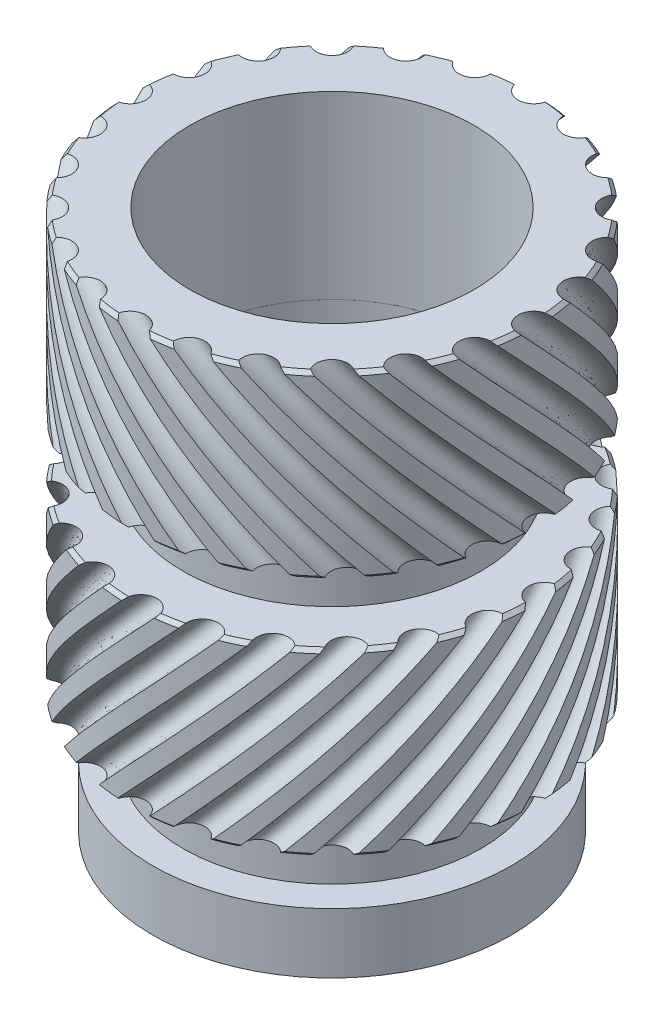
SolidWorks part; units mm, degrees
material "Brass"
ref_plane "Front" through (0, 0, 0) normal (0, 0, 1) x (1, 0, 0)
ref_plane "Top" through (0, 0, 0) normal (0, 1, 0) x (1, 0, 0)
ref_plane "Right" through (0, 0, 0) normal (1, 0, 0) x (0, 0, -1)
sketch "Layout " plane through (0, 0, 0) normal (0, 0, 1) x (1, 0, 0)
  line L0 (0, 0) -> (0, 9.5) construction
  line L1 (2.6222, 1.0556) -> (3.15, 1.0556) construction
  line L2 (3.15, 0) -> (0, 0) construction
  line L3 (3.55, 9.5) -> (3.55, 6.3333) construction
  line L4 (3.55, 6.3333) -> (2.6222, 6.3333) construction
  line L5 (2.6222, 6.3333) -> (2.6222, 5.2778) construction
  line L6 (2.6222, 5.2778) -> (3.55, 5.2778) construction
  line L7 (3.55, 5.2778) -> (3.55, 2.1111) construction
  line L8 (3.55, 2.1111) -> (2.6222, 2.1111) construction
  line L9 (2.6222, 2.1111) -> (2.6222, 1.0556) construction
  line L10 (2.6222, 5.8056) -> (0, 5.8056) construction
  line L11 (3.15, 1.0556) -> (3.15, 0) construction
  line L12 (0, 4.75) -> (2.5, 4.75) construction
  line L14 (3.55, 9.5) -> (3.55, 4.7136) construction
  line L15 (3.55, 9.5) -> (0, 9.5) construction
  line L16 (2.5, 9.5) -> (2.5, 0) construction
  point P19 (0, 8.7)
  dimension "D4" = 0.5278
  dimension "D5" = 3.1667
  dimension "D1" = 0.5278
ref_plane "Plane1" through (0, 5.8056, 0) normal (0, 1, 0) x (1, 0, 0)
sketch "Sketch3" plane through (0, 0, 0) normal (0, 0, 1) x (1, 0, 0)
  line L0 (0, 0) -> (0, 9.5) construction
  line L1 (3.55, 9.5) -> (0, 9.5) construction
  line L2 (3.55, 9.5) -> (3.55, 6.3333) construction
  line L4 (2.6222, 6.3333) -> (2.6222, 5.2778) construction
  line L5 (2.6222, 5.2778) -> (3.55, 5.2778) construction
  line L6 (3.55, 5.2778) -> (3.55, 2.1111) construction
  line L7 (2.6222, 2.1111) -> (2.6222, 1.0556) construction
  line L8 (3.55, 2.1111) -> (2.6222, 2.1111) construction
  line L9 (2.6222, 1.0556) -> (3.15, 1.0556) construction
  line L10 (3.15, 1.0556) -> (3.15, 0) construction
  line L11 (3.15, 0) -> (0, 0) construction
  line L12 (0, 6.3333) -> (0, 9.5)
  line L13 (3.55, 9.5) -> (0, 9.5)
  line L14 (3.55, 9.5) -> (3.55, 6.3333)
  line L16 (2.6222, 6.3333) -> (2.6222, 5.2778) construction
  line L17 (2.6222, 5.2778) -> (3.55, 5.2778) construction
  line L18 (3.55, 5.2778) -> (3.55, 2.1111) construction
  line L19 (2.6222, 2.1111) -> (2.6222, 1.0556) construction
  line L20 (3.55, 2.1111) -> (2.6222, 2.1111) construction
  line L21 (2.6222, 1.0556) -> (3.15, 1.0556) construction
  line L22 (3.15, 1.0556) -> (3.15, 0) construction
  line L23 (3.15, 0) -> (0, 0) construction
  line L25 (3.55, 6.3333) -> (0, 6.3333)
  line L26 (0, 6.3333) -> (0, 0) construction
revolve "Revolve1" add sketch "Sketch3" angle 360 about L12
sketch "Sketch4" plane through (0, 9.5, 0) normal (0, 1, 0) x (1, 0, 0)
  circle A1 centre (0, 0) radius 3.55
  circle A2 centre (0, 0) radius 3.55 construction
curve "Helix/Spiral1" pitch 23.75 height 9.5 radius 3.55 left hand yes centre (0, 9.5, 0) axis (0, -1, 0) start towards (-1, 0, 0)
sketch "Sketch6" plane through (0, 0, 0) normal (0, 0, 1) x (1, 0, 0)
  line L4 (2.6222, 6.3333) -> (2.6222, 5.2778) construction
  line L5 (3.55, 6.3333) -> (2.6222, 6.3333) construction
  line L9 (0, 0) -> (0, 9.5) construction
  line L10 (2.6222, 2.1111) -> (2.6222, 1.0556) construction
  line L11 (2.6222, 1.0556) -> (3.15, 1.0556) construction
  line L12 (3.15, 1.0556) -> (3.15, 0) construction
  line L13 (3.15, 0) -> (0, 0) construction
  line L14 (2.6222, 5.2778) -> (2.6222, 2.1111)
  line L18 (2.6222, 6.3333) -> (2.6222, 5.2778)
  line L19 (2.6222, 6.3333) -> (0, 6.3333)
  line L23 (0, 0) -> (0, 6.3333)
  line L24 (2.6222, 2.1111) -> (2.6222, 1.0556)
  line L25 (2.6222, 1.0556) -> (3.15, 1.0556)
  line L26 (3.15, 1.0556) -> (3.15, 0)
  line L27 (3.15, 0) -> (0, 0)
revolve "Revolve2" add sketch "Sketch6" angle 360 about L23
chamfer "Chamfer1" distance 0.0635 angle 45 2 edges at (3.55, 6.3333, 0) (3.55, 9.5, 0)
sketch "Sketch5" plane through (0, 9.5, 0) normal (0, 1, 0) x (1, 0, 0)
  line L0 (0, -3.55) -> (0, 0) construction
  line L1 (3.55, 0) -> (0, 0) construction
  line L2 (0, 0) -> (-0.2785, -3.5391) construction
  line L3 (0.2785, -3.5391) -> (0, 0) construction
  line L4 (-0.2785, -3.5391) -> (0, -3.55) construction
  line L5 (0, -3.55) -> (0, -3.2713) construction
  circle A0 centre (0, 0) radius 3.55 construction
  circle A1 centre (0, -3.55) radius 0.2787
  dimension "D1" = 9
sweep "Cut-Sweep1" cut profiles "Sketch5" path "Helix/Spiral1" align with end faces yes
pattern_circular "CirPattern1" count 24 over 360 about axis through (0, 6.3333, 0) along (0, -1, 0) of "Cut-Sweep1"
mirror "Mirror2" about plane through (0, 5.8056, 0) normal (0, 1, 0) of bodies 112 109
sketch "Sketch7" plane through (0, 9.5, 0) normal (0, 1, 0) x (1, 0, 0)
  circle A0 centre (0, 0) radius 2.5
extrude "Cut-Extrude1" cut sketch "Sketch7" against normal through all
sketch "Sketch8" plane through (0, 9.5, 0) normal (0, 1, 0) x (1, 0, 0)
  circle A0 centre (0, 0) radius 2.5 construction
  circle A1 centre (0, 0) radius 2.5
curve "Helix/Spiral2" [suppressed] pitch 0.8 height 10.3 turns 12.875
sketch "Sketch9" [suppressed] plane through (0, 0, 0) normal (0, 0, 1) x (1, 0, 0)
  line L0 (-2.5, 9.5) -> (-2.5, 10.2) construction
  line L1 (-1.9804, 9.8) -> (-1.9804, 9.9) construction
  line L2 (-1.9804, 9.8) -> (-2.5, 9.5) construction
  line L3 (-2.2402, 9.85) -> (-2.5, 9.85) construction
  line L4 (-2.5, 9.5) -> (-1.8938, 9.85) construction
  line L5 (-2.5, 10.2) -> (-1.8938, 9.85) construction
  line L6 (-2.2402, 9.65) -> (-2.2402, 10.05) construction
  line L7 (-2.5, 10.2) -> (-1.9804, 9.9) construction
  line L8 (-2.5, 9.5) -> (-2.5, 10.2)
  line L9 (-2.5, 10.2) -> (-1.9804, 9.9)
  line L10 (-1.9804, 9.9) -> (-1.9804, 9.8)
  line L11 (-1.9804, 9.8) -> (-2.5, 9.5)
sweep "Sweep2" [suppressed] add profiles "Sketch9" path "Helix/Spiral2"
sketch "Sketch10" [suppressed] plane through (0, 9.5, 0) normal (0, 1, 0) x (1, 0, 0)
  circle A0 centre (0, 0) radius 3 construction
  circle A1 centre (0, 0) radius 2.9365
  dimension "D1" = 0.0635
  dimension "D2" = 6
extrude "Cut-Extrude2" [suppressed] cut sketch "Sketch10" against normal through all draft 50 and the other way blind 2.54 draft 45
sketch "Sketch11" [suppressed] plane through (0, 0, 0) normal (0, -1, 0) x (1, 0, 0)
  circle A0 centre (0, 0) radius 2.6222
extrude "Cut-Extrude4" [suppressed] cut sketch "Sketch11" against normal through all draft 45 and the other way through all draft 45
combine bodies "Combine1" [suppressed] operation type add bodies to combine 129 119 126 124
equation "\"D5@Layout \"=\"Installed Length@Layout \"/3"
equation "\"D1@CirPattern1\"=360/15"
equation "\"D3@Helix/Spiral1\"=\"Installed Length@Layout \""
equation "\"D1@Sketch9\"=\"D2@Sketch9\"*.25"
equation "\"D1@Sketch9\"=\"D2@Sketch9\"/4"
equation "\"D2@Sketch9\"=\"Pitch@Layout \"*.5"
equation "\"D3@Helix/Spiral2\"=\"Installed Length@Layout \"+\"Pitch@Layout \""
equation "\"D4@Layout \"=\"D1@Layout \""
equation "\"D4@Helix/Spiral2\"=\"Pitch@Layout \""
